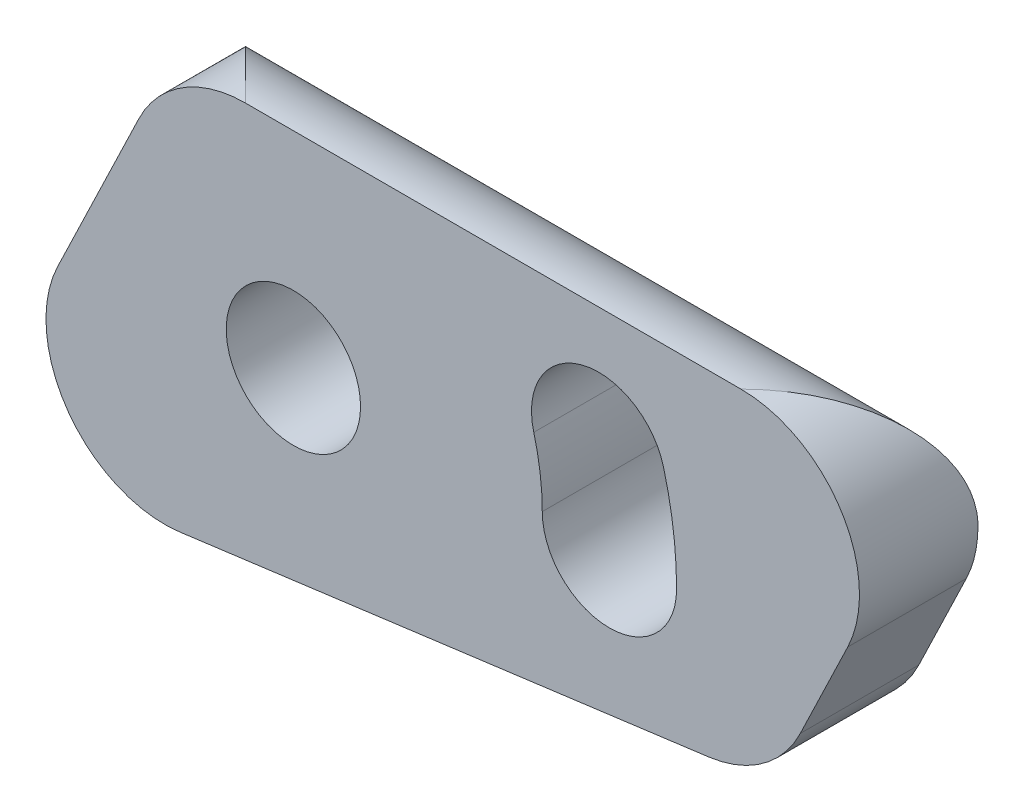
SolidWorks part; units mm, degrees
ref_plane "Front Plane" through (0, 0, 0) normal (0, 0, 1) x (1, 0, 0)
ref_plane "Top Plane" through (0, 0, 0) normal (0, 1, 0) x (1, 0, 0)
ref_plane "Right Plane" through (0, 0, 0) normal (1, 0, 0) x (0, 0, -1)
sketch "Esquisse1" plane through (0, 0, 0) normal (0, 0, 1) x (1, 0, 0)
  line L1 (12.5949, 9.1158) -> (-7.9044, 6.417)
  line L2 (6.6619, -3.2074) -> (15.5123, 15.1755) construction
  line L3 (-50, 0.875) -> (13.0442, 9.1749) construction
  line L4 (-7.9044, 6.417) -> (-2.6285, 17.3755)
  line L5 (-3.6877, 15.1755) -> (-6.0284, 10.3137) construction
  line L6 (12.5949, 9.1158) -> (16.5715, 17.3755)
  line L7 (16.5715, 17.3755) -> (-2.6285, 17.3755)
  line L8 (15.5123, 15.1755) -> (-3.6877, 15.1755) construction
  circle A0 centre (8.468, 12.1755) radius 1.7 construction
  circle A1 centre (8.468, 12.1755) radius 1.7
  circle A2 centre (0.468, 12.1755) radius 1.7
  circle A3 centre (0.468, 12.1755) radius 1.7 construction
  dimension "D1" = 3.5
extrude "Boss.-Extru.1" add sketch "Esquisse1" along normal blind 3
sketch "Esquisse2" plane through (0, 0, 3) normal (0, 0, 1) x (1, 0, 0)
  line L0 (8.468, 12.1755) -> (0.468, 12.1755) construction
  line L1 (0.468, 12.1755) -> (8.1954, 14.2461) construction
  arc A0 (6.768, 12.1755) -> (6.5533, 13.8061) centre (0.468, 12.1755) ccw
  circle A1 centre (8.468, 12.1755) radius 1.7 construction
  arc A2 (10.168, 12.1755) -> (9.8375, 14.6861) centre (0.468, 12.1755) ccw
  arc A3 (9.8375, 14.6861) -> (6.5533, 13.8061) centre (8.1954, 14.2461) ccw
  arc A4 (8.468, 12.1755) -> (8.1954, 14.2461) centre (0.468, 12.1755) ccw construction
  arc A5 (10.168, 12.1755) -> (6.768, 12.1755) centre (8.468, 12.1755) cw
  dimension "D1" = 15
extrude "Enlèv. mat.-Extru.1" cut sketch "Esquisse2" against normal through all
fillet "Congé1" radius 3 4 edges at (12.5949, 9.1158, 1.5) (16.5715, 17.3755, 1.5) (-2.6285, 17.3755, 1.5) (-7.9044, 6.417, 1.5)
fillet "Congé2" radius 3 1 edges at (5.5272, 17.3755, 0) tangent propagation no
